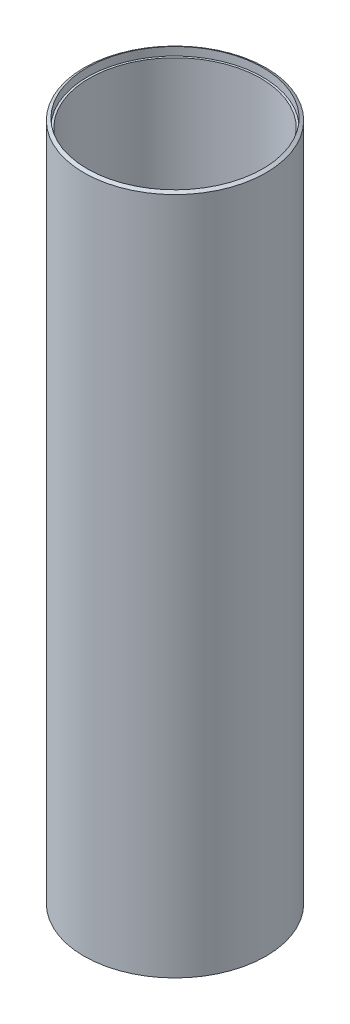
SolidWorks part; units mm, degrees
material "6061-T6 (SS)"
ref_plane "Front Plane" through (0, 0, 0) normal (0, 0, 1) x (1, 0, 0)
ref_plane "Top Plane" through (0, 0, 0) normal (0, 1, 0) x (1, 0, 0)
ref_plane "Right Plane" through (0, 0, 0) normal (1, 0, 0) x (0, 0, -1)
ref_axis "Axis1" through (0, 819.187, 0) along (0, -1, 0)
sketch "Sketch2" plane through (0, 0, 0) normal (0, 0, 1) x (1, 0, 0)
  line L0 (-69.85, 1.4298) -> (-69.85, 522.1298)
  line L1 (-67.3735, 0) -> (-69.85, 1.4298)
  line L2 (-65.786, 6.35) -> (-65.786, 517.2096)
  line L3 (-67.3735, 0) -> (-67.3735, 6.35)
  line L4 (-69.85, 261.7798) -> (-65.786, 261.7798) construction
  line L5 (0, 819.187) -> (0, -55) construction
  line L6 (-67.3735, 523.5596) -> (-69.85, 522.1298)
  line L7 (-67.3735, 517.2096) -> (-65.786, 517.2096)
  line L8 (-67.3735, 523.5596) -> (-67.3735, 517.2096)
  line L9 (-67.3735, 6.35) -> (-65.786, 6.35)
  line L13 (55, 0) -> (-55, 0) construction
  point P0 (0, 0)
  point P1 (-69.85, 261.7798)
  point P17 (-65.786, 261.7798)
  dimension "D2" = 4.064
  dimension "D3" = 260.35
  dimension "D4" = 69.85
  dimension "D6" = 60
  dimension "D10" = 1.5875
  dimension "D11" = 6.35
revolve "Revolve1" add sketch "Sketch2" angle 360 about axis through (0, 819.187, 0) along (0, -1, 0)
